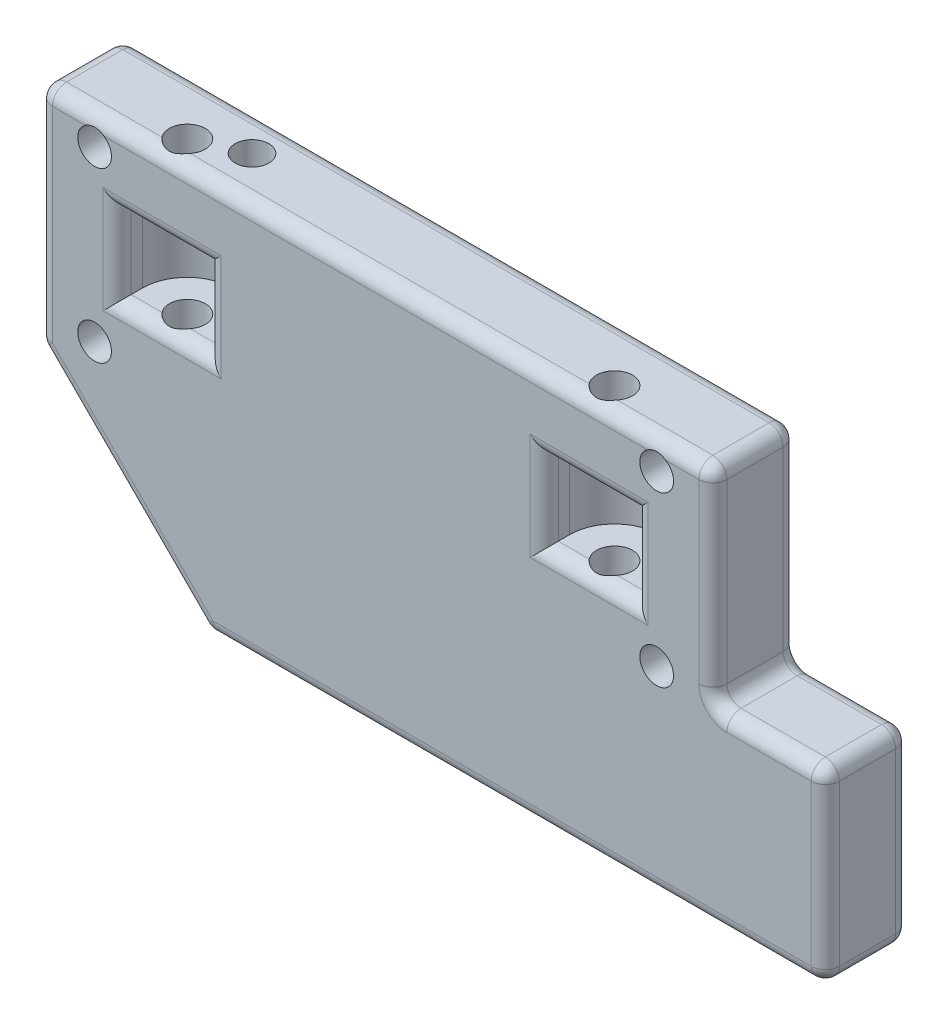
SolidWorks part; units mm, degrees
ref_plane "Front Plane" through (0, 0, 0) normal (0, 0, 1) x (1, 0, 0)
ref_plane "Top Plane" through (0, 0, 0) normal (0, 1, 0) x (1, 0, 0)
ref_plane "Right Plane" through (0, 0, 0) normal (1, 0, 0) x (0, 0, -1)
sketch "Sketch1" plane through (0, 0, 0) normal (0, 0, 1) x (1, 0, 0)
  line L0 (0, 0) -> (19.05, -19.05)
  line L2 (0, 0) -> (0, 25.4)
  line L3 (0, 25.4) -> (76.2, 25.4)
  line L5 (19.05, -19.05) -> (76.2, -19.05)
  line L7 (76.2, -19.05) -> (88.9, -19.05)
  line L8 (88.9, -19.05) -> (88.9, 2.2307)
  line L9 (88.9, 2.2307) -> (76.2, 2.2307)
  line L10 (76.2, 2.2307) -> (76.2, 25.4)
  dimension "D1" = 76.2
  dimension "D2" = 25.4
  dimension "D3" = 19.05
  dimension "D4" = 19.05
  dimension "D5" = 12.7
extrude "Boss-Extrude1" add sketch "Sketch1" along normal blind 9.525
ref_plane "Plane1" through (0, 12.7, 0) normal (0, 1, 0) x (1, 0, 0)
ref_plane "Plane2" through (38.1, 0, 0) normal (1, 0, 0) x (0, 0, -1)
sketch "Sketch2" plane through (0, 0, 9.525) normal (0, 0, 1) x (1, 0, 0)
  line L1 (0, 25.4) -> (0, 0) construction
  circle A0 centre (6.35, 22.225) radius 1.905
  dimension "D1" = 3.81
  dimension "D2" = 22.225
  dimension "D3" = 6.35
extrude "Cut-Extrude1" cut sketch "Sketch2" against normal through all
sketch "Sketch4" plane through (0, 12.7, 0) normal (0, 1, 0) x (1, 0, 0)
  line L7 (76.2, -9.525) -> (0, -9.525) construction
  line L8 (8.89, -6.6675) -> (8.89, -9.525)
  line L9 (19.05, -6.6675) -> (19.05, -9.525)
  line L10 (19.05, -9.525) -> (8.89, -9.525)
  line L11 (0, -9.525) -> (0, 0) construction
  arc A2 (19.05, -6.6675) -> (8.89, -6.6675) centre (13.97, -6.6675) ccw
  dimension "D1" = 10.16
  dimension "D2" = 2.8575
  dimension "D3" = 13.97
extrude "Cut-Extrude2" cut sketch "Sketch4" against normal mid plane 8.89
sketch "Sketch5" plane through (0, 25.4, 0) normal (0, 1, 0) x (1, 0, 0)
  line L0 (76.2, -9.525) -> (0, -9.525) construction
  line L1 (0, -9.525) -> (0, 0) construction
  circle A0 centre (13.97, -6.6675) radius 2.032
  dimension "D3" = 4.064
  dimension "D1" = 2.8575
  dimension "D2" = 13.97
extrude "Cut-Extrude3" cut sketch "Sketch5" against normal blind 28.575
sketch "Sketch13" plane through (0, 0, 0) normal (-1, 0, 0) x (0, 0, 1)
  line L0 (9.525, 25.4) -> (0, 25.4) construction
  line L1 (4.7625, 12.7) -> (0, 12.7) construction
  line L4 (4.7625, 12.7) -> (9.525, 12.7) construction
  circle A0 centre (4.7625, 12.7) radius 1.905
  dimension "D1" = 3.81
  dimension "D2" = 12.7
extrude "Cut-Extrude8" cut sketch "Sketch13" against normal blind 6.35
sketch "Sketch14" plane through (0, 0, 0) normal (0, 0, -1) x (-1, 0, 0)
  line L0 (-76.2, 25.4) -> (0, 25.4) construction
  line L1 (0, 25.4) -> (0, 0) construction
  circle A0 centre (-25.4, 22.225) radius 2.032
  dimension "D2" = 4.064
  dimension "D1" = 3.175
  dimension "D3" = 25.4
extrude "Cut-Extrude9" cut sketch "Sketch14" against normal blind 6.35
sketch "Sketch15" plane through (0, -19.05, 0) normal (0, -1, 0) x (1, 0, 0)
  line L0 (0, 9.525) -> (0, 0) construction
  line L1 (25.4, 0) -> (25.4, 4.7625) construction
  line L2 (19.05, 0) -> (88.9, 0) construction
  line L3 (25.4, 4.7625) -> (25.4, 9.525) construction
  line L4 (19.05, 9.525) -> (88.9, 9.525) construction
  circle A0 centre (25.4, 4.7625) radius 2.032
  dimension "D2" = 4.064
  dimension "D1" = 25.4
extrude "Cut-Extrude10" cut sketch "Sketch15" against normal blind 6.35
sketch "Sketch16" plane through (0, 25.4, 0) normal (0, 1, 0) x (1, 0, 0)
  line L0 (0, -9.525) -> (0, 0) construction
  line L1 (19.05, -4.4406) -> (19.05, 0.6437) construction
  line L2 (19.05, -4.4406) -> (19.05, -9.525) construction
  line L3 (76.2, 0) -> (0, 0) construction
  circle A0 centre (19.05, -4.4406) radius 1.905
  dimension "D2" = 3.81
  dimension "D1" = 19.05
extrude "Cut-Extrude11" cut sketch "Sketch16" against normal blind 6.35
mirror "Mirror1" about plane through (0, 12.7, 0) normal (0, 1, 0) of "Cut-Extrude1"
mirror "Mirror2" about plane through (38.1, 0, 0) normal (1, 0, 0) of "Cut-Extrude10", "Cut-Extrude9", "Cut-Extrude2", "Cut-Extrude1", "Mirror1", "Cut-Extrude3"
fillet "Fillet2" radius 1.5875 29 edges at (0, 0, 4.7625) (9.525, -9.525, 9.525) (19.05, -19.05, 4.7625) (9.525, -9.525, 0) (0, 25.4, 4.7625) (38.1, 25.4, 0) (0, 12.7, 0) (0, 12.7, 9.525) (53.975, -19.05, 9.525) (53.975, -19.05, 0) (62.23, 8.255, 9.525) (67.31, 12.7, 9.525) (62.23, 17.145, 9.525) (57.15, 12.7, 9.525) (19.05, 12.7, 9.525) (13.97, 17.145, 9.525) (8.89, 12.7, 9.525) (13.97, 8.255, 9.525) (38.1, 25.4, 9.525) (82.55, 2.2307, 9.525) (82.55, 2.2307, 0) (76.2, 2.2307, 4.7625) (76.2, 13.8153, 9.525) (76.2, 25.4, 4.7625) (76.2, 13.8153, 0) (88.9, -19.05, 4.7625) (88.9, -8.4097, 9.525) (88.9, 2.2307, 4.7625) (88.9, -8.4097, 0)
